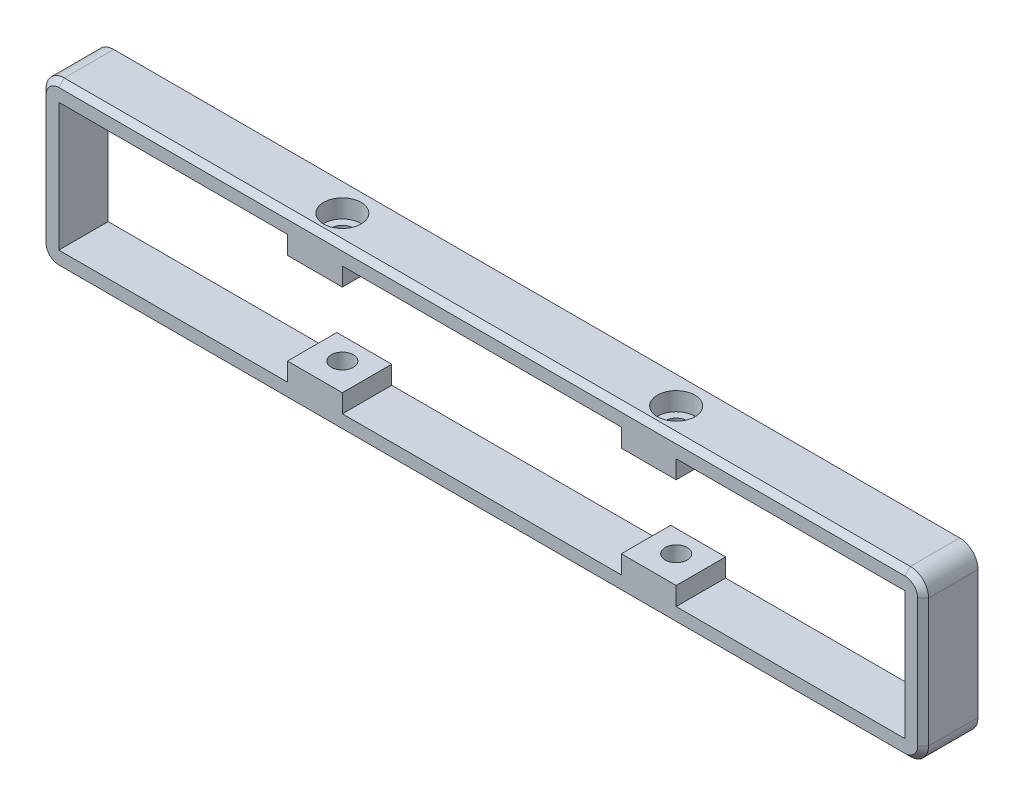
SolidWorks part; units mm, degrees
ref_plane "前视基准面" through (0, 0, 0) normal (0, 0, 1) x (1, 0, 0)
ref_plane "上视基准面" through (0, 0, 0) normal (0, 1, 0) x (1, 0, 0)
ref_plane "右视基准面" through (0, 0, 0) normal (1, 0, 0) x (0, 0, -1)
sketch "草图1" plane through (0, 0, 0) normal (0, 0, 1) x (1, 0, 0)
  line L0 (-46.25, 7) -> (-46.25, -7)
  line L1 (-48.25, 9) -> (48.25, 9)
  line L2 (-48.25, 9) -> (-48.25, -9)
  line L3 (-48.25, -9) -> (48.25, -9)
  line L4 (48.25, 9) -> (48.25, -9)
  line L5 (-48.25, 9) -> (48.25, -9) construction
  line L6 (-48.25, -9) -> (48.25, 9) construction
  line L7 (-46.25, -7) -> (46.25, -7)
  line L8 (46.25, 7) -> (46.25, -7)
  line L9 (-46.25, 7) -> (46.25, 7)
  point P0 (0, 0)
  dimension "D1" = 2
  dimension "D2" = 18
  dimension "D3" = 96.5
extrude "凸台-拉伸1" add sketch "草图1" along normal blind 6
fillet "圆角1" radius 2 4 edges at (-48.25, -9, 3) (48.25, -9, 3) (48.25, 9, 3) (-48.25, 9, 3)
chamfer "倒角1" distance 0.6 angle 45 4 edges at (46.25, 0, 0) (0, 7, 0) (0, -7, 0) (-46.25, 0, 0)
sketch "草图2" plane through (0, 0, 6) normal (0, 0, 1) x (1, 0, 0)
  line L0 (-18.25, 18.0172) -> (-18.25, -19.1432) construction
  line L1 (-48.25, 7) -> (-48.25, -7) construction
  line L2 (18.25, 15.2749) -> (18.25, -19.1432) construction
  line L3 (48.25, -7) -> (48.25, 7) construction
  line L4 (46.25, 7) -> (-46.25, 7) construction
  line L5 (-21.25, 7) -> (-15.25, 7)
  line L6 (-21.25, 7) -> (-21.25, 5)
  line L7 (-21.25, 5) -> (-15.25, 5)
  line L8 (-15.25, 7) -> (-15.25, 5)
  line L9 (-46.25, -7) -> (46.25, -7) construction
  line L10 (-21.25, -7) -> (-15.25, -7)
  line L11 (-21.25, -7) -> (-21.25, -5)
  line L12 (-21.25, -5) -> (-15.25, -5)
  line L13 (-15.25, -7) -> (-15.25, -5)
  line L15 (15.25, 7) -> (21.25, 7)
  line L16 (15.25, 7) -> (15.25, 5)
  line L17 (15.25, 5) -> (21.25, 5)
  line L18 (21.25, 7) -> (21.25, 5)
  line L19 (15.25, -7) -> (21.25, -7)
  line L20 (15.25, -7) -> (15.25, -5)
  line L21 (15.25, -5) -> (21.25, -5)
  line L22 (21.25, -7) -> (21.25, -5)
  dimension "D1" = 30
  dimension "D2" = 30
  dimension "D3" = 6
  dimension "D4" = 2
extrude "凸台-拉伸2" add sketch "草图2" against normal blind 5.4
sketch "草图3" plane through (0, 9, 0) normal (0, 1, 0) x (1, 0, 0)
  line L0 (-15.25, -6) -> (-21.25, -6) construction
  line L1 (-21.25, -6) -> (-21.25, -0.6) construction
  line L2 (-21.25, -0.6) -> (-15.25, -0.6) construction
  line L3 (-15.25, -0.6) -> (-15.25, -6) construction
  line L4 (21.25, -6) -> (15.25, -6) construction
  line L5 (15.25, -6) -> (15.25, -0.6) construction
  line L6 (15.25, -0.6) -> (21.25, -0.6) construction
  line L7 (21.25, -0.6) -> (21.25, -6) construction
  line L8 (-15.25, -6) -> (-21.25, -6) construction
  line L9 (-21.25, -6) -> (-21.25, -0.6) construction
  line L10 (-21.25, -0.6) -> (-15.25, -0.6) construction
  line L11 (-15.25, -0.6) -> (-15.25, -6) construction
  line L12 (21.25, -6) -> (15.25, -6) construction
  line L13 (15.25, -6) -> (15.25, -0.6) construction
  line L14 (15.25, -0.6) -> (21.25, -0.6) construction
  line L15 (21.25, -0.6) -> (21.25, -6) construction
  circle A0 centre (-18.25, -3) radius 1.2
  circle A1 centre (18.25, -3) radius 1.2
  point P2 (18.25, -6)
  point P4 (0, 0)
  point P14 (0, 0)
  dimension "D1" = 2.4
  dimension "D2" = 3
  dimension "D3" = 3
  dimension "D4" = 3
  dimension "D5" = 3
extrude "切除-拉伸1" cut sketch "草图3" against normal through all
sketch "草图4" plane through (0, 9, 0) normal (0, 1, 0) x (1, 0, 0)
  circle A0 centre (-18.25, -3) radius 2.05
  circle A1 centre (18.25, -3) radius 2.05
  dimension "D1" = 4.1
extrude "切除-拉伸2" cut sketch "草图4" against normal blind 2
extrude "切除-拉伸3" cut sketch "草图4<2>" along normal blind 2 from surface starting at face at (-18.25, -9, 4.2)
sketch "草图4<2>" plane through (0, 9, 0) normal (0, 1, 0) x (1, 0, 0) same geometry as "草图4"
chamfer "倒角2" distance 0.6 angle 45 8 edges at (0, 9, 6) (-47.6642, 8.4142, 6) (47.6642, 8.4142, 6) (-48.25, 0, 6) (48.25, 0, 6) (-47.6642, -8.4142, 6) (47.6642, -8.4142, 6) (0, -9, 6)
